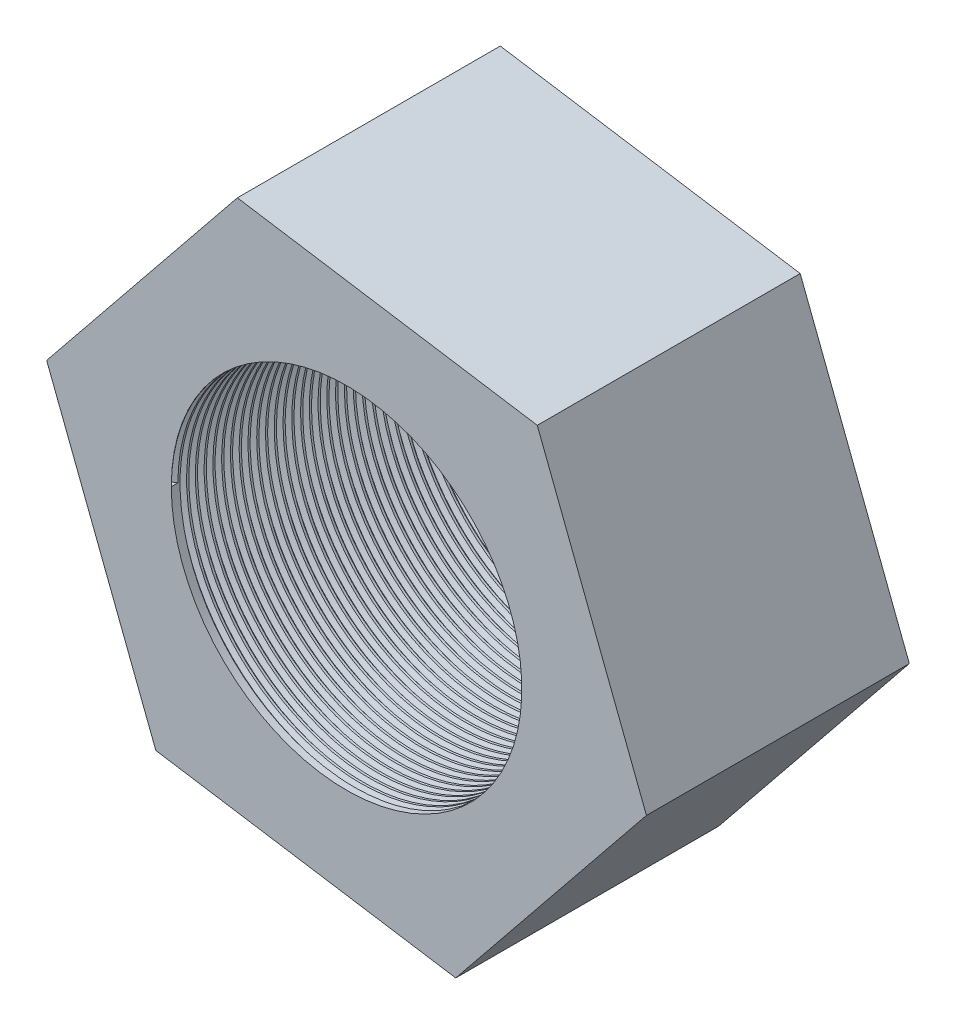
SolidWorks part; units mm, degrees
ref_plane "Front" through (0, 0, 0) normal (0, 0, 1) x (1, 0, 0)
ref_plane "Top" through (0, 0, 0) normal (0, 1, 0) x (1, 0, 0)
ref_plane "Right" through (0, 0, 0) normal (1, 0, 0) x (0, 0, -1)
sketch "Sketch1" plane through (0, 0, 0) normal (0, 0, 1) x (1, 0, 0)
  line L1 (10.8654, -1.7061) -> (6.9102, 8.5566)
  line L2 (6.9102, 8.5566) -> (-3.9551, 10.2628)
  line L3 (-3.9551, 10.2628) -> (-10.8654, 1.7061)
  line L4 (-10.8654, 1.7061) -> (-6.9102, -8.5566)
  line L5 (-6.9102, -8.5566) -> (3.9551, -10.2628)
  line L6 (3.9551, -10.2628) -> (10.8654, -1.7061)
  circle A0 centre (0, 0) radius 9.525 construction
  circle A1 centre (0, 0) radius 6.35
  dimension "D1" = 19.05
  dimension "D2" = 12.7
extrude "Boss-Extrude1" add sketch "Sketch1" along normal blind 9.525
thread "Thread1" pitch 0.3175 method cut profile "Thread Profile1" start angle 0, offset 0, length 12.7, pitch 0.3175, diameter 12.7
ref_plane "Plane1" through (-6.35, 0, 9.525) normal (0, -1, 0) x (-1, 0, 0)
sketch "Thread Profile1" plane through (-6.35, 0, 9.525) normal (0, -1, 0) x (-1, 0, 0)
  line L0 (0, 0) -> (0, 0.3175) construction
  line L1 (0, 0) -> (0.1719, 0.0992)
  line L2 (0.1719, 0.0992) -> (0.1719, 0.1389)
  line L3 (0.1719, 0.1389) -> (0, 0.2381)
  line L4 (0.1719, 0.1191) -> (0, 0.1191) construction
  line L11 (0, 0) -> (0, 0.2381)
  point P2 (0, 0)
  dimension "Pitch" = 0.3175
  dimension "Profile_Angle" = 60
  dimension "Profile_Land" = 0.0397
  dimension "Profile_Height" = 0.1719
